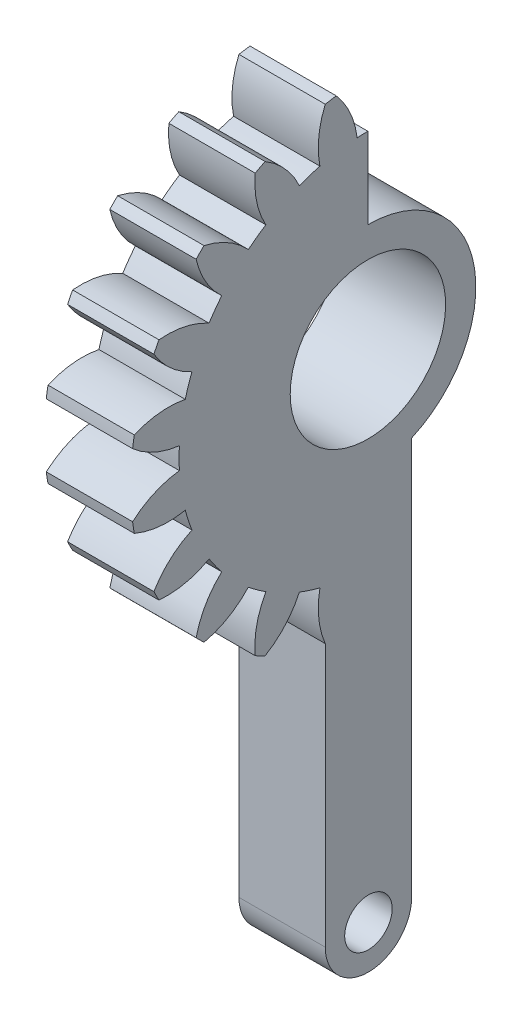
SolidWorks part; units mm, degrees
ref_plane "Plane1" through (0, 0, 0) normal (0, 0, 1) x (1, 0, 0)
ref_plane "Plane2" through (0, 0, 0) normal (0, 1, 0) x (1, 0, 0)
ref_plane "Plane3" through (0, 0, 0) normal (1, 0, 0) x (0, 0, -1)
sketch "HoldingSke" plane through (0, 0, 0) normal (0, 1, 0) x (1, 0, 0)
  line L0 (0, 0) -> (0.9397, -0.342)
  line L1 (-15, 0) -> (100, 0) construction
  line L2 (0, 0) -> (-2.1039, 2.3779)
  line L3 (0, 0) -> (-11.863, 4.5341)
  line L4 (0, 0) -> (8.1152, 2.9537)
  line L5 (0, 0) -> (-46.8476, -17.4728)
  line L6 (0, 0) -> (-1.6579, -1.1186)
  line L7 (-2.1039, 2.3779) -> (8.6586, 51.2059)
  line L8 (-76.2, 54.61) -> (-75.9, 54.61)
  line L9 (-71.009, 38.7566) -> (-53.1078, 45.2721)
  line L10 (-76.2, 71.12) -> (104.1128, 71.12)
  line L11 (0, 0) -> (-2, 0)
  line L12 (-76.2, 101.6) -> (-76.162, 101.6)
  line L13 (24.9733, 27.94) -> (52.9518, 28.4284)
  line L14 (24.9733, 27.94) -> (24.9743, 27.94)
  line L15 (24.9733, 27.94) -> (100.4006, 29.5858)
  line L16 (-63.627, -1) -> (-12.827, -1)
  circle A0 centre (0, 0) radius 1
  circle A1 centre (0, 0) radius 8.749
  circle A2 centre (0, 0) radius 37.5
  circle A3 centre (0, 0) radius 1
  dimension "MHD" = 17.498
  dimension "Hub_dia" = 75
  dimension "Bore" = 2
  dimension "MBD" = 2
  dimension "Num_teeth" = 20
  dimension "Pitch" = 1
  dimension "Overall_len" = 50
  dimension "Show_teeth" = 20
  dimension "Thickness" = 2
  dimension "OAL" = 50.0001
  dimension "T_dim" = 0.3
  dimension "Ap" = 20
  dimension "H" = 19.05
  dimension "Pitch_radius" = 180.3128
  dimension "Width" = 2
  dimension "Backlash" = 0.038
  dimension "Addendum_fac" = 1
  dimension "Dedendum_fac" = 1.25
  dimension "Clearance_fac" = 0.25
  dimension "Dedendum_add" = 0.001
  dimension "Module" = 1
sketch "BasProSke" plane through (0, 0, 0) normal (0, 1, 0) x (1, 0, 0)
  line L0 (-10, 0) -> (60, 0) construction
  line L1 (0, 0) -> (0, 11)
  line L2 (0, 0) -> (4, 0)
  line L3 (4, 0) -> (4, 11)
  line L4 (4, 11) -> (0, 11)
  dimension "Thickness" = 4
  dimension "Diameter" = 22
revolve "Base-Revolve" add sketch "BasProSke" angle 360 about L0
sketch "TooCutSke" plane through (0, 0, 0) normal (1, 0, 0) x (0, 0, -1)
  line L1 (0, 0) -> (0, 107) construction
  line L2 (0, 0) -> (-0.8511, 9.9637) construction
  line L3 (0, 0) -> (-3.1206, 19.7028) construction
  line L4 (-0.8511, 9.9637) -> (-1.5603, 9.8514) construction
  arc A0 (0.4999, 8.7347) -> (-0.4999, 8.7347) centre (0, 0) ccw
  arc A1 (1.4852, 10.9249) -> (-1.4852, 10.9249) centre (0, 0) ccw
  circle A2 centre (0, 0) radius 10 construction
  circle A3 centre (0, 0) radius 9.3969 construction
  arc A4 (-0.4999, 8.7347) -> (-1.4852, 10.9249) centre (-4.4722, 8.2645) ccw
  arc A5 (1.4852, 10.9249) -> (0.4999, 8.7347) centre (4.4722, 8.2645) ccw
  dimension "Root_dia" = 17.498
  dimension "Overcut_dia" = 22.0508
  dimension "Pitch_dia" = 20
  dimension "Base_dia" = 18.7939
  dimension "Flank_rad" = 4
  dimension "Half_ang" = 9
  dimension "Half_CT" = 0.7181
extrude "ToothCut" cut sketch "TooCutSke" along normal through all
fillet "Breaks" [suppressed] radius 0.02 tangent propagation no
fillet "RootFillets" [suppressed] radius 0.251
pattern_circular "TeethCuts" count 20 every 18 about axis through (-10, 0, 0) along (1, 0, 0) of "ToothCut", "RootFillets", "Breaks"
sketch "HubNeaOneSke" plane through (0, 0, 0) normal (-1, 0, 0) x (0, 0, 1)
  circle A0 centre (0, 0) radius 8.749
  dimension "Diameter" = 17.498
extrude "HubNearOne" [suppressed] add sketch "HubNeaOneSke" along normal blind 46.0001
sketch "HubNeaBotSke" plane through (0, 0, 0) normal (-1, 0, 0) x (0, 0, 1)
  circle A0 centre (0, 0) radius 8.749
  dimension "Diameter" = 17.498
extrude "HubNearBoth" [suppressed] add sketch "HubNeaBotSke" along normal blind 23
ref_plane "FarPln" through (4, 0, 0) normal (1, 0, 0) x (0, 0, -1)
sketch "HubFarSke" plane through (4, 0, 0) normal (1, 0, 0) x (0, 0, -1)
  circle A0 centre (0, 0) radius 8.749
  dimension "Diameter" = 17.498
extrude "HubFar" [suppressed] add sketch "HubFarSke" along normal blind 23
sketch "BorSke" plane through (0, 0, 0) normal (1, 0, 0) x (0, 0, -1)
  circle A0 centre (0, 0) radius 1
  dimension "Diameter" = 2
extrude "Bore" cut sketch "BorSke" along normal mid plane 100.0001
sketch "KeySke" plane through (0, 0, 0) normal (1, 0, 0) x (0, 0, -1)
  line L0 (-0.4, 0) -> (-0.4, 1.3)
  line L1 (-0.4, 1.3) -> (0.4, 1.3)
  line L2 (0.4, 1.3) -> (0.4, 0)
  line L3 (0, 0) -> (0, 34) construction
  line L4 (-0.4, 0) -> (0.4, 0)
  dimension "Offset" = 1.3
  dimension "Width" = 0.8
extrude "Keyway" [suppressed] cut sketch "KeySke" along normal mid plane 100.0001
pattern_circular "Keyway2" [suppressed] count 2 every 90 about axis through (-10, 0, 0) along (1, 0, 0) reverse direction yes
sketch "草图1" plane through (4, 0, 0) normal (1, 0, 0) x (0, 0, -1)
  line L0 (0, 2.5) -> (0, 12.4015)
  line L1 (0, 12.4015) -> (15.1933, 12.4015)
  line L2 (15.1933, 12.4015) -> (15.1933, -15.03)
  line L3 (15.1933, -15.03) -> (0, -15.03)
  line L4 (0, -15.03) -> (0, -2.5)
  circle A0 centre (0, 0) radius 2.5
  dimension "D1" = 5
extrude "切除-拉伸1" cut sketch "草图1" against normal blind 10 contours A0 L4 L3 L2 L1 L0 region at (4, -1.3459, -7.7543)
ref_plane "基准面1" through (0, -25, 0) normal (0, 1, 0) x (1, 0, 0)
sketch "草图3" plane through (0, -25, 0) normal (0, 1, 0) x (1, 0, 0)
  line L0 (4, 0) -> (4, 2.5) construction
  line L1 (4, -1.9757) -> (4, 2.0243)
  line L2 (0, 2.5) -> (0, 0) construction
  line L3 (0, 2.0243) -> (0, -1.9757)
  line L5 (0, -1.9757) -> (4, -1.9757) construction
  line L6 (0, -1.9757) -> (4, -1.9757)
  line L7 (4, 2.0243) -> (0, 2.0243)
  dimension "D1" = 4
extrude "凸台-拉伸1" add sketch "草图3" along normal up to next
fillet "圆角1" radius 2 2 edges at (2, -25, 1.9757) (2, -25, -2.0243)
sketch "草图4" plane through (4, 0, 0) normal (1, 0, 0) x (0, 0, -1)
  arc A0 (0.0243, -25) -> (2.0243, -23) centre (0.0243, -23) ccw construction
  arc A1 (0.0243, -25) -> (2.0243, -23) centre (0.0243, -23) ccw
  circle A2 centre (0.0243, -23) radius 1.1
  dimension "D1" = 2.2
extrude "切除-拉伸2" cut sketch "草图4" against normal blind 10 contours A2 region at (4, -23, -0.0243)
sketch "草图5" plane through (0, 0, 0) normal (-1, 0, 0) x (0, 0, 1)
  circle A0 centre (0, 0) radius 1 construction
  circle A1 centre (0, 0) radius 1
extrude "凸台-拉伸2" add sketch "草图5" against normal up to surface (4 mm away)
sketch "草图6" plane through (0, 0, 0) normal (-1, 0, 0) x (0, 0, 1)
  arc A0 (0, 2.5) -> (-2.0243, -1.467) centre (0, 0) ccw construction
  arc A1 (0, 2.5) -> (-2.0243, -1.467) centre (0, 0) ccw
  circle A2 centre (0, 0) radius 5
  line M2 (-2.0243, -1.467) -> (-2.0243, -23)
  line M44 (0, 8.749) -> (0, 2.5)
  arc M45 (0, 2.5) -> (-2.0243, -1.467) centre (0, 0) ccw
  dimension "D1" = 10
extrude "凸台-拉伸3" add sketch "草图6" along normal blind 1 contours A2 M2 M44 M45 | A2 M44 M2 M45 region at (0, -0.3483, 1.2343) region at (0, 0.7892, -2.7969)
sketch "草图7" plane through (0, 0, 0) normal (1, 0, 0) x (0, 0, -1)
  line L2 (0, 5) -> (0, 2.5)
  line L3 (2.0243, -1.467) -> (2.0243, -4.5719)
  line L4 (0, 5) -> (0, 2.5)
  line L5 (2.0243, -1.467) -> (2.0243, -4.5719)
  arc A2 (2.0243, -1.467) -> (0, 2.5) centre (0, 0) ccw
  arc A3 (2.0243, -4.5719) -> (0, 5) centre (0, 0) ccw
  arc A4 (2.0243, -1.467) -> (0, 2.5) centre (0, 0) ccw
  arc A5 (2.0243, -4.5719) -> (0, 5) centre (0, 0) ccw
  dimension "D1" = 0
extrude "凸台-拉伸4" add sketch "草图7" along normal up to surface (4 mm away)
sketch "草图8" plane through (4, 0, 0) normal (1, 0, 0) x (0, 0, -1)
  circle A0 centre (0, 0) radius 3.6
  dimension "D1" = 7.2
extrude "切除-拉伸3" cut sketch "草图8" against normal blind 3.2
sketch "草图10" plane through (-1, 0, 0) normal (-1, 0, 0) x (0, 0, 1)
  circle A0 centre (0, 0) radius 3.6
  dimension "D1" = 7.2
extrude "切除-拉伸4" cut sketch "草图10" against normal blind 23.2
sketch "草图11" plane through (4, 0, 0) normal (1, 0, 0) x (0, 0, -1)
  circle A0 centre (0, 0) radius 3.6 construction
  circle A1 centre (0, 0) radius 3.6
extrude "凸台-拉伸5" add sketch "草图11" against normal blind 1
sketch "草图12" plane through (3, 0, 0) normal (-1, 0, 0) x (0, 0, 1)
  circle A0 centre (0, 0) radius 3.6
  dimension "D1" = 7.2
extrude "切除-拉伸5" cut sketch "草图12" against normal blind 1
sketch "草图13" plane through (-1, 0, 0) normal (-1, 0, 0) x (0, 0, 1)
  line L0 (2.2275, 2.8281) -> (14.1395, 1.9951)
  line L1 (-1000, 0) -> (49000, 0) construction
  line L4 (2.2275, -2.8281) -> (14.1395, -1.9951)
  line L5 (6, -2.5643) -> (6, 2.5643)
  line L6 (-2.0243, -4.5719) -> (-2.0243, -23) construction
  circle A0 centre (0, 0) radius 3.6 construction
  circle A1 centre (0, 0) radius 3.6
  circle A3 centre (14, 0) radius 2
  circle M4 centre (0, 0) radius 5
  circle M9 centre (0, 0) radius 3.6
  dimension "D1" = 2
  dimension "D2" = 14
  dimension "D3" = 4
  dimension "D4" = 6
extrude "切除-拉伸6" cut sketch "草图13" against normal blind 1.8 contours L1 L5 L0 M4 | L1 L4 L5 M4 | L1 L0 M9 M4 | L1 A1 L4 M4 region at (-1, 1.4426, 5.3505) region at (-1, 1.441, 3.9354) region at (-1, -1.4426, 5.3505) region at (-1, -1.441, 3.9354)
equation "' \"Module@HoldingSke\" = 6.35"
equation "' \"Num_teeth@HoldingSke\" = 12"
equation "' \"Ap@HoldingSke\" =  20"
equation "' \"Ap@HoldingSke\" = 20"
equation "' \"Width@HoldingSke\" = 0.5 * 25.4"
equation "' \"Hub_dia@HoldingSke\"= 1 * 25.4"
equation "' \"Hub_dia@HoldingSke\" = 1 * 25.4"
equation "' \"Overall_len@HoldingSke\" = 1.0 * 25.4"
equation "' \"Bore@HoldingSke\" = 0.75 * 25.4"
equation "' \"T_dim@HoldingSke\" = 0.1 * 25.4"
equation "' \"Width@KeySke\" = 0.25 * 25.4"
equation "' \"Show_teeth@HoldingSke\" = 13"
equation "' \"Backlash@HoldingSke\" = 0.009 * 25.4"
equation "' \"Addendum_fac@HoldingSke\" = 1.0"
equation "' \"Dedendum_fac@HoldingSke\" = 1.25"
equation "' \"Dedendum_add@HoldingSke\" = 0.00005 * 25.4"
equation "' \"Clearance_fac@HoldingSke\" = 0.25"
equation "\"Pitch@HoldingSke\" = 1 / \"Module@HoldingSke\""
equation "\"Overcut_dia@TooCutSke\" = (\"Num_teeth@HoldingSke\" + 2 * \"Addendum_fac@HoldingSke\") / \"Pitch@HoldingSke\" + 0.002 * 25.4"
equation "\"Pitch_dia@TooCutSke\" = \"Num_teeth@HoldingSke\" / \"Pitch@HoldingSke\""
equation "\"Base_dia@TooCutSke\" = \"Num_teeth@HoldingSke\" / \"Pitch@HoldingSke\" * cos((\"Ap@HoldingSke\"  * 3.14159265 / 180))"
equation "\"Root_dia@TooCutSke\" = (\"Num_teeth@HoldingSke\" + 2) / \"Pitch@HoldingSke\" - 2 * (\"Addendum_fac@HoldingSke\" + \"Dedendum_fac@HoldingSke\") / \"Pitch@HoldingSke\" - \"Dedendum_add@HoldingSke\" * 2"
equation "\"Half_ang@TooCutSke\" = 180 / \"Num_teeth@HoldingSke\""
equation "\"Half_CT@TooCutSke\" = \"Num_teeth@HoldingSke\" / \"Pitch@HoldingSke\" * sin((3.14159265 / 2 / \"Num_teeth@HoldingSke\")) / 2 - 7 * \"Backlash@HoldingSke\" / 4"
equation "\"Flank_rad@TooCutSke\" = \"Num_teeth@HoldingSke\" / \"Pitch@HoldingSke\" / 5"
equation "\"Radius@RootFillets\" = \"Clearance_fac@HoldingSke\" / \"Pitch@HoldingSke\" + \"Dedendum_add@HoldingSke\""
equation "\"Break_rad@Breaks\" = 0.02 / \"Pitch@HoldingSke\""
equation "\"Thickness@HoldingSke\" = \"Width@HoldingSke\""
equation "\"OAL@HoldingSke\" = \"Thickness@HoldingSke\""
equation "\"MHD@HoldingSke\" = (\"Num_teeth@HoldingSke\" + 2) / \"Pitch@HoldingSke\" - 2 * (\"Addendum_fac@HoldingSke\" + \"Dedendum_fac@HoldingSke\")  / \"Pitch@HoldingSke\" - \"Dedendum_add@HoldingSke\" * 2"
equation "\"MBD@HoldingSke\" = (\"Num_teeth@HoldingSke\" + 2) / \"Pitch@HoldingSke\" - 2 * (\"Addendum_fac@HoldingSke\" + \"Dedendum_fac@HoldingSke\")  / \"Pitch@HoldingSke\" - \"Dedendum_add@HoldingSke\" * 2 - 0.002 * 25.4"
equation "\"MHD@HoldingSke\" = ((sgn( \"MHD@HoldingSke\" - \"Hub_dia@HoldingSke\" )-1)*( \"MHD@HoldingSke\" - \"Hub_dia@HoldingSke\" ))/-2+ \"Hub_dia@HoldingSke\""
equation "\"MBD@HoldingSke\" = ((sgn( \"MBD@HoldingSke\" - \"Bore@HoldingSke\" )-1)*( \"MBD@HoldingSke\" - \"Bore@HoldingSke\" ))/-2+ \"Bore@HoldingSke\""
equation "\"OAL@HoldingSke\" = ((sgn( \"OAL@HoldingSke\" - \"Overall_len@HoldingSke\" )+1)*( \"OAL@HoldingSke\" - \"Overall_len@HoldingSke\" ))/2 + \"Overall_len@HoldingSke\" + 0.000002 * 25.4"
equation "\"Num_teeth@TeethCuts\" = int( \"Show_teeth@HoldingSke\" ) + 1"
equation "\"Num_teeth@TeethCuts\" = ((sgn( \"Num_teeth@TeethCuts\" - \"Num_teeth@HoldingSke\" )-1)*( \"Num_teeth@TeethCuts\" - \"Num_teeth@HoldingSke\" ))/-2+ \"Num_teeth@HoldingSke\""
equation "\"Num_teeth@TeethCuts\" = ((sgn( \"Num_teeth@TeethCuts\" - 2.0)+1)*( \"Num_teeth@TeethCuts\" - 2.0))/2 +2.0"
equation "\"Angle@TeethCuts\" = 360.0 / \"Num_teeth@HoldingSke\""
equation "\"Diameter@BasProSke\" = (\"Num_teeth@HoldingSke\" + 2 * \"Addendum_fac@HoldingSke\") / \"Pitch@HoldingSke\""
equation "' \"Fillet_rad@BasProSke\" =  \"Thickness@HoldingSke\" * 0.05"
equation "' \"Fillet_rad@BasProSke\" = \"Thickness@HoldingSke\" * 0.05"
equation "\"MHD@HoldingSke\" = ((sgn( \"MHD@HoldingSke\" - \"Root_dia@TooCutSke\" )-1)*( \"MHD@HoldingSke\" - \"Root_dia@TooCutSke\" ))/-2+ \"Root_dia@TooCutSke\""
equation "\"Diameter@HubNeaOneSke\" = \"MHD@HoldingSke\""
equation "\"Length@HubNearOne\" = \"OAL@HoldingSke\" - \"Thickness@BasProSke\""
equation "\"Diameter@HubNeaBotSke\" = \"MHD@HoldingSke\""
equation "\"Length@HubNearBoth\" = ( \"OAL@HoldingSke\" - \"Thickness@BasProSke\" ) / 2.0"
equation "\"Thickness@FarPln\" = \"Thickness@BasProSke\""
equation "\"Diameter@HubFarSke\" = \"MHD@HoldingSke\""
equation "\"Length@HubFar\" = ( \"OAL@HoldingSke\" - \"Thickness@BasProSke\" ) / 2.0"
equation "\"Diameter@BorSke\" = \"MBD@HoldingSke\""
equation "\"D1@Bore\" = \"OAL@HoldingSke\" * 2.0"
equation "\"D1@Keyway\" = \"OAL@HoldingSke\" * 2.0"
equation "\"Offset@KeySke\" = \"T_dim@HoldingSke\" + \"MBD@HoldingSke\" / 2.0"
